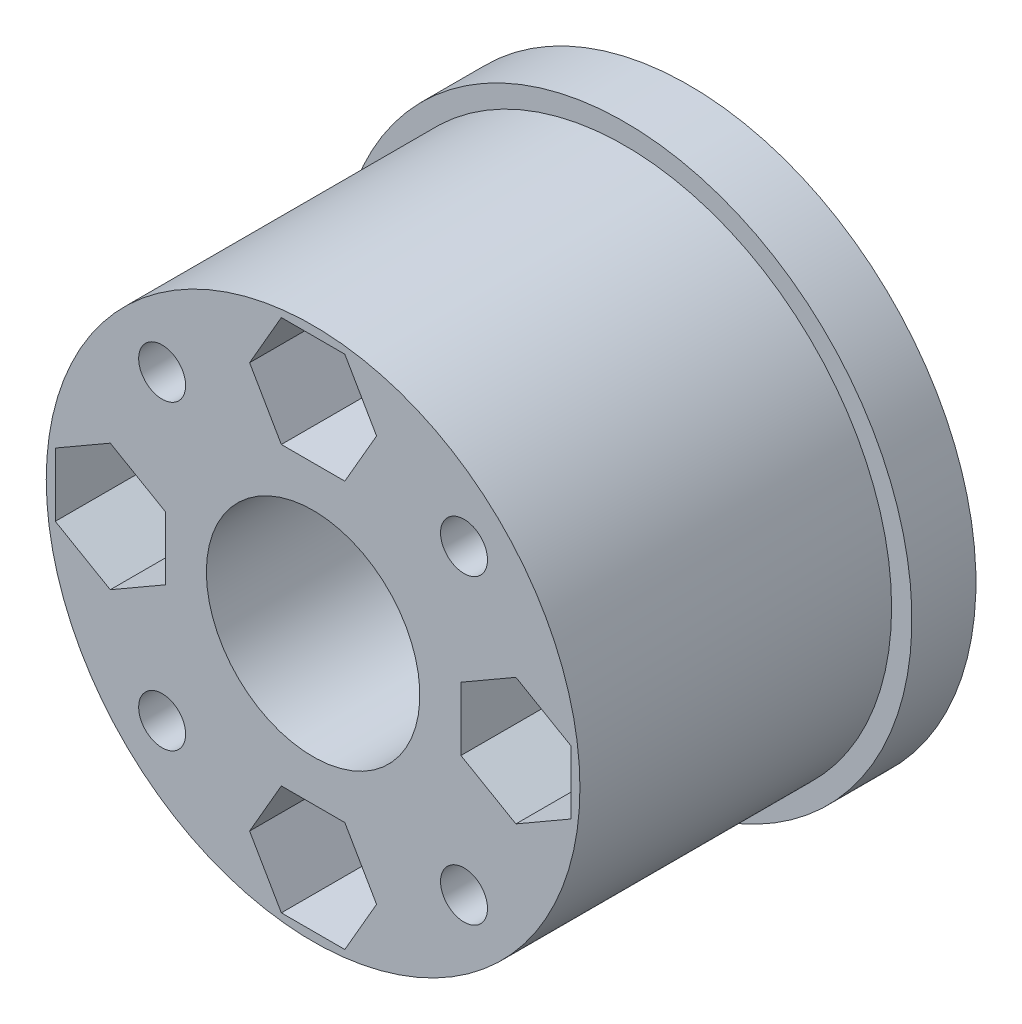
SolidWorks part; units mm, degrees
ref_plane "Front Plane" through (0, 0, 0) normal (0, 0, 1) x (1, 0, 0)
ref_plane "Top Plane" through (0, 0, 0) normal (0, 1, 0) x (1, 0, 0)
ref_plane "Right Plane" through (0, 0, 0) normal (1, 0, 0) x (0, 0, -1)
ref_axis "Z" through (0, 0, 15.48) along (0, 0, -1)
ref_plane "Plane1" through (0, 0, 0) normal (0.7071, 0.7071, 0) x (0, 0, -1)
sketch "Sketch10" plane through (0, 0, 0) normal (0, 1, 0) x (1, 0, 0)
  line L0 (-13.45, 3) -> (-7.5, 3)
  line L1 (0, 38.469) -> (0, 33.6342) construction
  line L2 (0, -15.48) -> (0, 3.88) construction
  line L3 (-13.45, 3) -> (-13.45, 0)
  line L4 (-13.45, 0) -> (-12.5, 0)
  line L5 (-12.5, 0) -> (-12.5, -14.6)
  line L10 (-12.5, -17.2) -> (-11, -17.2) construction
  line L11 (-11, -17.2) -> (-11, -16.2) construction
  line L12 (-11, -16.2) -> (-5, -16.2) construction
  line L14 (-7.5, 3) -> (-7.5, 2)
  line L15 (-7.5, 2) -> (-5, 2)
  line L18 (-5, 2) -> (-5, -14.6)
  line L19 (-12.5, -14.6) -> (-5, -14.6)
  line L20 (-5, -16.2) -> (-5, -14.6)
  line L21 (-12.5, -14.6) -> (-12.5, -17.2)
  dimension "D1" = 25
  dimension "D2" = 26.9
  dimension "D4" = 3
  dimension "D3" = 17.2
  dimension "D8" = 1
  dimension "D9" = 11
  dimension "D11" = 1
  dimension "D12" = 15
  dimension "D5" = 14.6
  dimension "D10" = 10
revolve "Revolve1" add sketch "Sketch10" angle 360 about L1
sketch "Sketch11" plane through (0, 0, 0) normal (0, 0, 1) x (1, 0, 0)
  line L0 (9.5, 0) -> (0, 0) construction
  circle A0 centre (9.5, 0) radius 1.325
  dimension "D2" = 2.65
  dimension "D1" = 9.5
extrude "AttachmentBoltHoles" cut sketch "Sketch11" against normal through all both and the other way through all
sketch "Sketch13" plane through (0, 0, -3) normal (0, 0, -1) x (-1, 0, 0)
  line L0 (-7.0711, 7.0711) -> (0, 0) construction
  line L1 (-9.5, 0) -> (0, 0) construction
  circle A0 centre (-7.0711, 7.0711) radius 1.975
  dimension "D2" = 3.95
  dimension "D1" = 45
  dimension "D3" = 10
extrude "ShaftBoltHead" cut sketch "Sketch13" against normal blind 2.2
sketch "Sketch14" plane through (0, 0, 0) normal (0, 0, 1) x (1, 0, 0)
  circle A0 centre (7.0711, 7.0711) radius 1.1
  dimension "D1" = 2.2
extrude "ShaftBoltThru" cut sketch "Sketch14" along normal through all both and the other way through all
sketch "Sketch12" plane through (0, 0, 14.6) normal (0, 0, 1) x (1, 0, 0)
  line L0 (9.5, 0) -> (0, 0) construction
  line L1 (12.075, -1.4867) -> (12.075, 1.4867)
  line L2 (12.075, 1.4867) -> (9.5, 2.9734)
  line L3 (9.5, 2.9734) -> (6.925, 1.4867)
  line L4 (6.925, 1.4867) -> (6.925, -1.4867)
  line L5 (6.925, -1.4867) -> (9.5, -2.9734)
  line L6 (9.5, -2.9734) -> (12.075, -1.4867)
  circle A0 centre (9.5, 0) radius 2.575 construction
  dimension "D1" = 5.15
extrude "NutHole" cut sketch "Sketch12" against normal offset from surface (12.6 mm away) 5 up to face at (5.0961, 7.0711, -3)
pattern_circular "CirPattern1" count 4 over 360 about axis through (0, 0, 15.48) along (0, 0, -1) of "AttachmentBoltHoles", "NutHole", "ShaftBoltThru", "ShaftBoltHead"
sketch "Sketch15" [suppressed] plane through (0, 0, 0) normal (0, 1, 0) x (1, 0, 0)
  line L0 (-4, -15) -> (-13.45, -15)
  line L1 (-12.5, -15) -> (-5, -15) construction
  line L2 (-13.45, -15) -> (-13.45, -17.6)
  line L3 (0, -10.5706) -> (0, -16.964) construction
  line L4 (-13.45, -17.6) -> (-5.45, -17.6)
  line L5 (-12.5, -17.6) -> (-11, -17.6) construction
  line L6 (-5.45, -17.6) -> (-5.45, -16.6)
  line L7 (-5.45, -16.6) -> (-4, -16.6)
  line L8 (-4, -16.6) -> (-4, -15)
  dimension "D1" = 26.9
  dimension "D2" = 10.9
  dimension "D3" = 1
  dimension "D4" = 8
revolve "Revolve2" [suppressed] add sketch "Sketch15" angle 360 about L3
sketch "Sketch16" [suppressed] plane through (0, 0, 17.6) normal (0, 0, 1) x (1, 0, 0)
  line L0 (7.0711, 7.0711) -> (0, 0) construction
  line L1 (5.3768, 8.7653) -> (4.7567, 6.4509)
  line L2 (4.7567, 6.4509) -> (6.4509, 4.7567)
  line L3 (6.4509, 4.7567) -> (8.7653, 5.3768)
  line L4 (8.7653, 5.3768) -> (9.3854, 7.6912)
  line L5 (9.3854, 7.6912) -> (7.6912, 9.3854)
  line L18 (7.6912, 9.3854) -> (5.3768, 8.7653)
  circle A0 centre (7.0711, 7.0711) radius 2.075 construction
  circle A1 centre (7.0711, 7.0711) radius 1.1
  circle A2 centre (7.0711, 7.0711) radius 1.1 construction
  dimension "D3" = 4.15
  dimension "D2" = 0
extrude "Cut-Extrude1" [suppressed] cut sketch "Sketch16" against normal blind 1.7
sketch "Sketch17" [suppressed] plane through (0, 0, 17.6) normal (0, 0, 1) x (1, 0, 0)
  line L6 (12.075, -1.4867) -> (12.075, 1.4867)
  line L7 (12.075, 1.4867) -> (9.5, 2.9734)
  line L8 (9.5, 2.9734) -> (6.925, 1.4867)
  line L9 (6.925, 1.4867) -> (6.925, -1.4867)
  line L10 (6.925, -1.4867) -> (9.5, -2.9734)
  line L11 (9.5, -2.9734) -> (12.075, -1.4867)
  line L12 (12.075, -1.4867) -> (12.075, 1.4867)
  line L13 (12.075, 1.4867) -> (9.5, 2.9734)
  line L14 (9.5, 2.9734) -> (6.925, 1.4867)
  line L15 (6.925, 1.4867) -> (6.925, -1.4867)
  line L16 (6.925, -1.4867) -> (9.5, -2.9734)
  line L17 (9.5, -2.9734) -> (12.075, -1.4867)
  circle A1 centre (7.0711, 7.0711) radius 1.1
  circle A2 centre (7.0711, 7.0711) radius 1.1
  dimension "D1" = 0
  dimension "D2" = 0
extrude "Cut-Extrude2" [suppressed] cut sketch "Sketch17" against normal through all both and the other way through all
pattern_circular "CirPattern2" [suppressed] count 4 over 360 about axis through (0, 0, 15.48) along (0, 0, -1) of bodies 125
equation "\"BearingOD\"= 32"
equation "\"BearingHeight\"= 4"
equation "\"SeatsOD\"= \"BearingOD\" + 10"
equation "\"RetainingRingThickness\"= 1.30"
equation "\"BearingBaseDistance\"= 17.2 - 2*\"BearingHeight\"  - \"RetainingRingThickness\"*2"
equation "\"WireHarnessHeight\"= 4"
equation "\"OuterWallWidth\"= 6"
equation "\"OverallOD\"= 42"
equation "\"RetaininRingGrooveDiameter\"= 23.9"
equation "\"ShaftLengthAfterFlange\"= 2*\"BearingHeight\" + \"BearingBaseDistance\" + \"RetainingRingThickness\"*2\t'give a retaining ring thickness of extra clearance"
equation "\"RetainingRingGrooveBase\"= \"ShaftLengthAfterFlange\" - \"RetainingRingThickness\"*2"
equation "\"BearingID\"= 25"
equation "\"CoverClearance\"= 1"
equation "\"CoverThickness\"= 1"
equation "\"FlangHeight\"= 3"
equation "\"OuterHousingHeight\"= \"WireHarnessHeight\" + \"BearingHeight\"*2 + \"BearingBaseDistance\""
equation "\"PCBWidth\"= 5"
equation "\"PCBHeight\"= \"OuterHousingHeight\" "
equation "\"PCBThickness\"= 1"
equation "\"NormalDistSidewallPCBToZ\"= (\"OverallOD\"/2) - 1.6\t'radial distance from the z axis to pcb origin on the top/connector side"
equation "\"PCBSidewallCutoutClearance\"= 0.1"
equation "\"OutputHubBoltCircleRadius\"= 8"
equation "\"OutputHubOD\"= 27"
equation "\"StatorWireRadius\"= \"NormalDistSidewallPCBToZ\" - 5.7"
equation "\"MountingHoleRadius\"= (\"OverallOD\"+\"BearingOD\")/4"
equation "\"D1@Sketch10\"=\"BearingID\""
equation "\"BearingInnerRaceOD\"= 26.9"
equation "\"D2@Sketch10\"=\"BearingInnerRaceOD\""
equation "\"D4@Sketch10\"=\"FlangHeight\""
equation "\"D3@Sketch10\"=\"ShaftLengthAfterFlange\""
equation "\"D1@Sketch11\"=round(\"BearingID\"*0.75)/2"
equation "\"D9@Sketch10\"=10.8+0.2"
equation "\"D5@Sketch10\"=\"BearingBaseDistance\" + \"BearingHeight\"*2"
equation "\"D10@Sketch10\"=10"
equation "\"D3@Sketch13\"=\"BearingID\"/2-2.5"
equation "\"D1@Sketch15\"=\"BearingInnerRaceOD\""
equation "\"D2@Sketch15\"=10.9"
